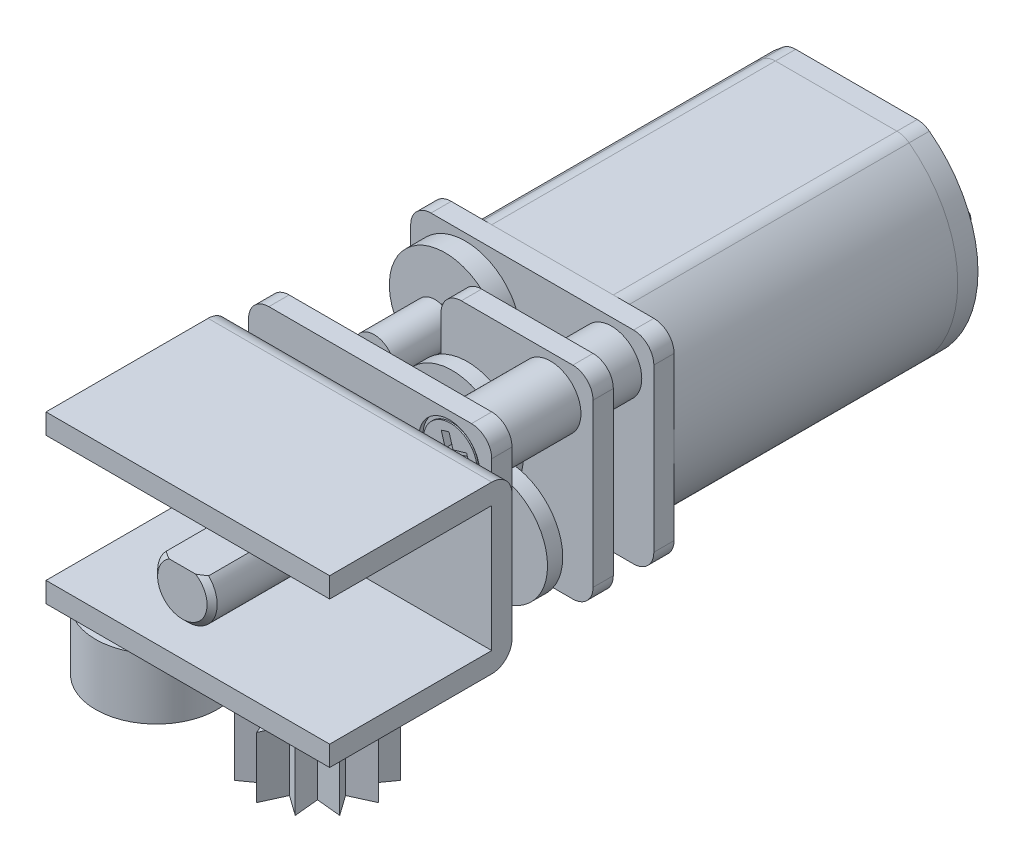
SolidWorks part; units mm, degrees
note: The reader was unsure of these and kept them because the rebuilt part matched: shared geometry of "Sketch2<2>", "Sketch9<3>", "Sketch12<2>", "Sketch29<3>".
material "Plain Carbon Steel"
ref_plane "Front Plane" through (0, 0, 0) normal (0, 0, 1) x (1, 0, 0)
ref_plane "Top Plane" through (0, 0, 0) normal (0, 1, 0) x (1, 0, 0)
ref_plane "Right Plane" through (0, 0, 0) normal (1, 0, 0) x (0, 0, -1)
sketch "Sketch1" plane through (0, 0, 0) normal (0, 0, 1) x (1, 0, 0)
  line L0 (3.3166, 5) -> (-3.3166, 5)
  line L1 (-3.3166, -5) -> (3.3166, -5)
  arc A0 (3.3166, -5) -> (3.3166, 5) centre (0, 0) ccw
  arc A1 (-3.3166, 5) -> (-3.3166, -5) centre (0, 0) ccw
  dimension "D1" = 12
  dimension "D2" = 10
extrude "Boss-Extrude1" add sketch "Sketch1" along normal mid plane 15
fillet "Fillet3" radius 1 4 edges at (-3.3166, -5, 0) (3.3166, -5, 0) (3.3166, 5, 0) (-3.3166, 5, 0)
sketch "Sketch2" plane through (0, 0, 7.5) normal (0, 0, 1) x (1, 0, 0)
  line L1 (-5, -5) -> (5, -5)
  line L2 (-6, -4) -> (-6, 4)
  line L3 (-5, 5) -> (5, 5)
  line L4 (6, -4) -> (6, 4)
  line L5 (-6, -5) -> (6, 5) construction
  line L6 (-6, 5) -> (6, -5) construction
  arc A0 (-5, -5) -> (-6, -4) centre (-5, -4) cw
  arc A1 (5, -5) -> (6, -4) centre (5, -4) ccw
  arc A2 (5, 5) -> (6, 4) centre (5, 4) cw
  arc A3 (-6, 4) -> (-5, 5) centre (-5, 4) cw
  point P0 (0, 0)
  dimension "D3" = 1
  dimension "D1" = 12
  dimension "D2" = 10
extrude "Boss-Extrude2" add sketch "Sketch2" along normal blind 1 separate body
extrude "Boss-Extrude3" add sketch "Sketch2<2>" against normal blind 1 from offset 9 separate body
sketch "Sketch2<2>" plane through (0, 0, 7.5) normal (0, 0, 1) x (1, 0, 0) same geometry as "Sketch2"
sketch "Sketch7" plane through (0, 0, 8.5) normal (0, 0, 1) x (1, 0, 0)
  line L0 (-3.1041, 2.1041) -> (3.1041, -2.1041) construction
  line L1 (0, 0) -> (0, 50000) construction
  line L2 (-6, 4) -> (-6, -4) construction
  line L3 (5, 5) -> (-5, 5) construction
  circle A0 centre (0, 0) radius 3.75 construction
  circle A1 centre (-3.1041, 2.1041) radius 0.5
  circle A2 centre (3.1041, -2.1041) radius 0.5
  circle A3 centre (-3.1041, 2.1041) radius 2.8959 construction
  point P3 (3.1041, -2.1041)
  point P4 (-3.1041, 2.1041)
  dimension "D1" = 7.5
  dimension "D3" = 1
extrude "Boss-Extrude5" add sketch "Sketch7" along normal up to surface (8 mm away) separate body up to face at (0, 0, 16.5)
sketch "Sketch11" plane through (0, 0, 8.5) normal (0, 0, 1) x (1, 0, 0)
  line L0 (-5, -1.25) -> (-2.5, -1.25)
  line L1 (-1.5, -0.25) -> (-1.5, 4)
  line L4 (-5, -5) -> (5, -5)
  line L5 (6, -4) -> (6, 4)
  line L6 (5, 5) -> (-5, 5)
  line L7 (-6, 4) -> (-6, -4)
  line L8 (-5, -5) -> (5, -5)
  line L9 (6, -4) -> (6, 4)
  line L10 (5, 5) -> (-0.5, 5)
  line L11 (-6, -2.25) -> (-6, -4)
  arc A0 (-1.5, 4) -> (-0.5, 5) centre (-0.5, 4) cw
  arc A1 (-2.5, -1.25) -> (-1.5, -0.25) centre (-2.5, -0.25) ccw
  arc A2 (-5, -1.25) -> (-6, -2.25) centre (-5, -2.25) ccw
  arc A4 (-6, -4) -> (-5, -5) centre (-5, -4) ccw
  arc A5 (5, -5) -> (6, -4) centre (5, -4) ccw
  arc A6 (6, 4) -> (5, 5) centre (5, 4) ccw
  arc A7 (-5, 5) -> (-6, 4) centre (-5, 4) ccw
  arc A8 (-6, -4) -> (-5, -5) centre (-5, -4) ccw
  arc A9 (5, -5) -> (6, -4) centre (5, -4) ccw
  arc A10 (6, 4) -> (5, 5) centre (5, 4) ccw
  dimension "D2" = 1
  dimension "D3" = 7.5
  dimension "D4" = 3.75
  dimension "D1" = 0
extrude "Boss-Extrude8" add sketch "Sketch11" along normal blind 1 from offset 2 separate body
sketch "Sketch5" plane through (0, 0, 16.5) normal (0, 0, 1) x (1, 0, 0)
  line L0 (5, 4) -> (-5, -4) construction
  circle A0 centre (0, 0) radius 0.75
  circle A1 centre (-3.1041, 2.1041) radius 0.38
  circle A2 centre (3.1041, -2.1041) radius 0.38
  circle A3 centre (0, 0) radius 5 construction
  circle A4 centre (3.9043, 3.1235) radius 0.75
  circle A5 centre (-3.9043, -3.1235) radius 0.75
  circle A6 centre (0, 0) radius 5.75 construction
  dimension "D1" = 1.5
  dimension "D2" = 0.76
  dimension "D3" = 11.5
  dimension "D4" = 1.5
extrude "Cut-Extrude1" cut sketch "Sketch5" against normal up to surface (9 mm away)
sketch "Sketch8" plane through (0, 0, 16.5) normal (0, 0, 1) x (1, 0, 0)
  circle A0 centre (-3.1041, 2.1041) radius 0.5
  circle A1 centre (3.1041, -2.1041) radius 0.5
  circle A2 centre (-3.1041, 2.1041) radius 0.5 construction
  circle A3 centre (-3.1041, 2.1041) radius 0.38
  circle A4 centre (3.1041, -2.1041) radius 0.38
  circle A5 centre (-3.1041, 2.1041) radius 0.38 construction
extrude "Cut-Extrude2" cut sketch "Sketch8" against normal blind 1
sketch "Sketch9" plane through (0, 0, 8.5) normal (0, 0, 1) x (1, 0, 0)
  circle A0 centre (-3.1041, 2.1041) radius 2.75
  circle A1 centre (-3.1041, 2.1041) radius 0.5
  circle A2 centre (-3.1041, 2.1041) radius 0.5 construction
  circle A3 centre (0, 0) radius 1
  circle M1 centre (0, 0) radius 0.75
  dimension "D1" = 5.5
  dimension "D2" = 2
extrude "Boss-Extrude6" add sketch "Sketch9" along normal blind 1 from offset 0.2 separate body contours A0 A1
extrude "Boss-Extrude16" add sketch "Sketch9<3>" along normal blind 1.3 from offset 0.1 separate body contours A3 M1 | M1
sketch "Sketch9<3>" plane through (0, 0, 8.5) normal (0, 0, 1) x (1, 0, 0) same geometry as "Sketch9"
sketch "Sketch6" plane through (0, 0, 16.5) normal (0, 0, 1) x (1, 0, 0)
  circle A0 centre (0, 0) radius 1.95
  circle A1 centre (0, 0) radius 0.75
  circle A2 centre (0, 0) radius 0.75 construction
  dimension "D1" = 3.9
extrude "Boss-Extrude4" add sketch "Sketch6" along normal blind 0.6
sketch "Sketch10" plane through (0, 0, 9.7) normal (0, 0, 1) x (1, 0, 0)
  circle A0 centre (-3.1041, 2.1041) radius 0.5
  circle A1 centre (-3.1041, 2.1041) radius 1
  circle A2 centre (0, 0) radius 2.75 construction
  circle A4 centre (-3.1041, 2.1041) radius 0.5 construction
  circle A5 centre (-3.1041, 2.1041) radius 2.75 construction
extrude "Boss-Extrude7" add sketch "Sketch10" along normal blind 3 from offset 0.5 separate body
sketch "Sketch12" plane through (0, 0, 8.5) normal (0, 0, 1) x (1, 0, 0)
  circle A0 centre (-3.9043, -3.1235) radius 0.75
  circle A1 centre (-3.9043, -3.1235) radius 1.5
  circle A2 centre (-3.9043, -3.1235) radius 0.75 construction
  circle A3 centre (3.9043, 3.1235) radius 0.75
  circle A4 centre (3.9043, 3.1235) radius 1.5
  dimension "D1" = 3
extrude "Boss-Extrude9" add sketch "Sketch12" along normal up to next (2 mm away) separate body
extrude "Boss-Extrude10" add sketch "Sketch12<2>" along normal up to next (7 mm away) from surface at 3 separate body starting at face at (0.75, 0, 11.5)
sketch "Sketch12<2>" plane through (0, 0, 8.5) normal (0, 0, 1) x (1, 0, 0) same geometry as "Sketch12"
sketch "Sketch13" plane through (0, 0, 17.1) normal (0, 0, 1) x (1, 0, 0)
  circle A0 centre (0, 0) radius 1.5
  dimension "D1" = 3
extrude "Cut-Extrude3" cut sketch "Sketch13" against normal up to next (7.2 mm away)
sketch "Sketch14" plane through (0, 0, 16.5) normal (0, 0, 1) x (1, 0, 0)
  circle A0 centre (3.9043, 3.1235) radius 1.5
  circle A1 centre (-3.9043, -3.1235) radius 1.5
  dimension "D1" = 3
extrude "Cut-Extrude4" cut sketch "Sketch14" against normal blind 0.2
chamfer "Chamfer1" distance 0.5 angle 45 2 edges at (-3.1543, -3.1235, 16.3) (4.6543, 3.1235, 16.3)
sketch "Sketch15" plane through (0, 0, 11.5) normal (0, 0, 1) x (1, 0, 0)
  circle A0 centre (0, 0) radius 2.75
  circle A1 centre (-3.1041, 2.1041) radius 1 construction
extrude "Boss-Extrude11" add sketch "Sketch15" along normal blind 0.75 from offset 0.2 separate body
sketch "Sketch16" plane through (0, 0, 12.45) normal (0, 0, 1) x (1, 0, 0)
  circle A0 centre (0, 0) radius 1
  circle A2 centre (0, 0) radius 1 construction
extrude "Boss-Extrude12" add sketch "Sketch16" along normal blind 1.15 from offset 0.2
sketch "Sketch17" plane through (0, 0, 12.45) normal (0, 0, 1) x (1, 0, 0)
  circle A0 centre (3.1041, -2.1041) radius 2.75
  circle A2 centre (0, 0) radius 1 construction
extrude "Boss-Extrude13" add sketch "Sketch17" along normal blind 0.75 from offset 0.4 separate body
sketch "Sketch18" plane through (0, 0, 13.6) normal (0, 0, 1) x (1, 0, 0)
  circle A0 centre (3.1041, -2.1041) radius 1
  circle A1 centre (0, 0) radius 1 construction
extrude "Boss-Extrude14" add sketch "Sketch18" along normal blind 1.5 from offset 0.2
sketch "Sketch19" plane through (0, 0, 15.3) normal (0, 0, 1) x (1, 0, 0)
  circle A0 centre (3.1041, -2.1041) radius 0.5
  circle A1 centre (3.1041, -2.1041) radius 0.5 construction
extrude "Cut-Extrude5" cut sketch "Sketch19" against normal through all
sketch "Sketch20" plane through (0, 0, 15.3) normal (0, 0, 1) x (1, 0, 0)
  circle A0 centre (0, 0) radius 2.75
  circle A1 centre (3.1041, -2.1041) radius 1 construction
extrude "Boss-Extrude15" add sketch "Sketch20" against normal blind 1 separate body
sketch "Sketch21" plane through (0, 0, 15.3) normal (0, 0, 1) x (1, 0, 0)
  circle A0 centre (0, 0) radius 0.5
  dimension "D1" = 1
extrude "Cut-Extrude6" cut sketch "Sketch21" against normal up to surface (7.8 mm away)
sketch "Sketch22" plane through (0, 0, 0) normal (0, 1, 0) x (1, 0, 0)
  line L0 (0, 0) -> (0, -50000) construction
  line L1 (-3, 7.5) -> (3, 7.5) construction
  line L2 (-0.5, -7.5) -> (-0.5, -15.3)
  line L3 (0.75, -7.5) -> (-0.75, -7.5) construction
  line L4 (-0.5, -15.3) -> (0.5, -15.3) construction
  line L5 (-0.5, -15.3) -> (-1.47, -15.3)
  line L6 (-2.75, -15.3) -> (2.75, -15.3) construction
  line L7 (-1.47, -15.3) -> (-1.47, -25.77)
  line L8 (-1.47, -25.77) -> (0, -25.77)
  line L9 (0, -25.77) -> (0, -7.5)
  line L10 (3, -7.5) -> (-3, -7.5) construction
  line L11 (0, -7.5) -> (-0.5, -7.5)
  line L12 (5, -16.5) -> (-5, -16.5) construction
  point P4 (0, 7.5)
  dimension "D1" = 1
  dimension "D2" = 2.94
  dimension "D3" = 9.27
revolve "Revolve1" add sketch "Sketch22" angle 360 about L0
chamfer "Chamfer2" distance 0.25 angle 45 1 edges at (-1.47, 0, 25.77)
sketch "Sketch23" plane through (0, 0, 25.77) normal (0, 0, 1) x (1, 0, 0)
  line L0 (1.0488, 1.03) -> (-1.0488, 1.03)
  circle A0 centre (0, 0) radius 1.47 construction
  arc A1 (1.0488, 1.03) -> (-1.0488, 1.03) centre (0, 0) ccw
  point P4 (0, -1.47)
  dimension "D1" = 2.5
extrude "Cut-Extrude7" cut sketch "Sketch23" against normal up to surface (8.67 mm away) up to face at (1.5, 0, 17.1)
sketch "Sketch24" plane through (0, 0, 16.5) normal (0, 0, 1) x (1, 0, 0)
  circle A0 centre (4.5, 0) radius 0.8
  circle A1 centre (-4.5, 0) radius 0.8
  dimension "D3" = 1.6
  dimension "D1" = 4.5
  dimension "D2" = 9
extrude "Cut-Extrude8" cut sketch "Sketch24" against normal up to next (1 mm away)
sketch "Sketch25" plane through (0, 0, -7.5) normal (0, 0, -1) x (-1, 0, 0)
  line L2 (-3, -5) -> (3, -5)
  line L3 (3, 5) -> (-3, 5)
  line L4 (-3, -5) -> (3, -5)
  line L5 (3, 5) -> (-3, 5)
  arc A2 (-3.6, 4.8) -> (-3.6, -4.8) centre (0, 0) ccw
  arc A3 (3.6, -4.8) -> (3.6, 4.8) centre (0, 0) ccw
  arc A4 (-3.6, 4.8) -> (-3.6, -4.8) centre (0, 0) ccw
  arc A5 (3.6, -4.8) -> (3.6, 4.8) centre (0, 0) ccw
  arc A10 (3, -5) -> (3.6, -4.8) centre (3, -4) ccw
  arc A11 (3, -5) -> (3.6, -4.8) centre (3, -4) ccw
  arc A12 (3.6, 4.8) -> (3, 5) centre (3, 4) ccw
  arc A13 (3.6, 4.8) -> (3, 5) centre (3, 4) ccw
  arc A14 (-3, 5) -> (-3.6, 4.8) centre (-3, 4) ccw
  arc A15 (-3, 5) -> (-3.6, 4.8) centre (-3, 4) ccw
  arc A16 (-3.6, -4.8) -> (-3, -5) centre (-3, -4) ccw
  arc A17 (-3.6, -4.8) -> (-3, -5) centre (-3, -4) ccw
  dimension "D1" = 0
extrude "Cut-Extrude9" cut sketch "Sketch25" against normal blind 1
sketch "Sketch26" plane through (0, 0, -6.5) normal (0, 0, -1) x (-1, 0, 0)
  line L2 (-3, -5) -> (3, -5)
  line L3 (3, 5) -> (-3, 5)
  line L4 (-3, -5) -> (3, -5)
  line L5 (3, 5) -> (-3, 5)
  arc A2 (-3.6, 4.8) -> (-3.6, -4.8) centre (0, 0) ccw
  arc A3 (3.6, -4.8) -> (3.6, 4.8) centre (0, 0) ccw
  arc A4 (-3.6, 4.8) -> (-3.6, -4.8) centre (0, 0) ccw
  arc A5 (3.6, -4.8) -> (3.6, 4.8) centre (0, 0) ccw
  arc A10 (-3.6, -4.8) -> (-3, -5) centre (-3, -4) ccw
  arc A11 (-3.6, -4.8) -> (-3, -5) centre (-3, -4) ccw
  arc A12 (3, -5) -> (3.6, -4.8) centre (3, -4) ccw
  arc A13 (3, -5) -> (3.6, -4.8) centre (3, -4) ccw
  arc A14 (3.6, 4.8) -> (3, 5) centre (3, 4) ccw
  arc A15 (3.6, 4.8) -> (3, 5) centre (3, 4) ccw
  arc A16 (-3, 5) -> (-3.6, 4.8) centre (-3, 4) ccw
  arc A17 (-3, 5) -> (-3.6, 4.8) centre (-3, 4) ccw
  dimension "D1" = 0
extrude "Boss-Extrude17" add sketch "Sketch26" along normal blind 1 separate body
sketch "Sketch27" plane through (0, 0, -7.5) normal (0, 0, -1) x (-1, 0, 0)
  circle A0 centre (0, 0) radius 2.5
  dimension "D1" = 5
extrude "Boss-Extrude18" add sketch "Sketch27" along normal blind 1.5
sketch "Sketch28" plane through (0, 0, -7.5) normal (0, 0, -1) x (-1, 0, 0)
  line L1 (3.35, 0.75) -> (3.65, 0.75)
  line L2 (3.35, 0.75) -> (3.35, -0.75)
  line L3 (3.35, -0.75) -> (3.65, -0.75)
  line L4 (3.65, 0.75) -> (3.65, -0.75)
  line L5 (3.35, 0.75) -> (3.65, -0.75) construction
  line L6 (3.35, -0.75) -> (3.65, 0.75) construction
  line L7 (-3.65, 0.75) -> (-3.35, 0.75)
  line L8 (-3.65, 0.75) -> (-3.65, -0.75)
  line L9 (-3.65, -0.75) -> (-3.35, -0.75)
  line L10 (-3.35, 0.75) -> (-3.35, -0.75)
  line L11 (-3.65, 0.75) -> (-3.35, -0.75) construction
  line L12 (-3.65, -0.75) -> (-3.35, 0.75) construction
  point P0 (3.5, 0)
  point P5 (-3.5, 0)
  dimension "D1" = 3.5
  dimension "D2" = 7
  dimension "D3" = 0.3
  dimension "D4" = 1.5
extrude "Boss-Extrude19" add sketch "Sketch28" along normal blind 2 separate body
fillet "Fillet1" radius 0.7 2 edges at (-3.5, -0.75, -9.5) (-3.5, 0.75, -9.5)
fillet "Fillet2" radius 0.7 2 edges at (3.5, -0.75, -9.5) (3.5, 0.75, -9.5)
ref_plane "Plane1" through (0, 0, 0) normal (0.6247, -0.7809, 0) x (0.7809, 0.6247, 0)
sketch "Sketch29" plane through (0, 0, 0) normal (0.6247, -0.7809, 0) x (0.7809, 0.6247, 0)
  line L0 (5, 16.5) -> (5, 50016.5) construction
  line L1 (6.5, 16.5) -> (3.5, 16.5) construction
  line L2 (-5, 16.5) -> (-5, 50016.5) construction
  line L3 (-3.5, 16.5) -> (-6.5, 16.5) construction
  line L4 (5.7, 7.5) -> (5.7, 15.755)
  line L5 (6, 7.5) -> (-0.1874, 7.5) construction
  line L6 (5.7, 15.755) -> (6.325, 16.38)
  line L7 (6.325, 16.38) -> (6.325, 16.45)
  line L8 (6.325, 16.45) -> (5, 16.45)
  line L9 (5, 16.45) -> (5, 7.5)
  line L10 (4.25, 7.5) -> (5.75, 7.5) construction
  line L11 (5, 7.5) -> (5.7, 7.5)
  line L12 (2.1864, 16.5) -> (7.184, 16.5) construction
  line L13 (0, 0) -> (0, 50000) construction
  line L14 (-5, 7.5) -> (-5.7, 7.5)
  line L15 (-5, 16.45) -> (-5, 7.5)
  line L16 (-6.325, 16.45) -> (-5, 16.45)
  line L17 (-6.325, 16.38) -> (-6.325, 16.45)
  line L18 (-5.7, 15.755) -> (-6.325, 16.38)
  line L19 (-5.7, 7.5) -> (-5.7, 15.755)
  point P4 (5, 16.5)
  point P9 (-5, 16.5)
  dimension "D1" = 45
  dimension "D2" = 1.4
  dimension "D3" = 2.65
  dimension "D4" = 0.05
  dimension "D5" = 0.07
revolve "Revolve2" add sketch "Sketch29" angle 360 about L0
revolve "Revolve3" add sketch "Sketch29<3>" angle 360 about L2
sketch "Sketch29<3>" plane through (0, 0, 0) normal (0.6247, -0.7809, 0) x (0.7809, 0.6247, 0) same geometry as "Sketch29"
sketch "Sketch30" plane through (0, 0, 16.45) normal (0, 0, 1) x (1, 0, 0)
  line L0 (-3.5871, -2.2813) -> (-4.2216, -3.9657) construction
  line L1 (-3.7742, -2.2107) -> (-4.021, -2.8658)
  line L2 (-4.7466, -2.8062) -> (-3.0621, -3.4408) construction
  line L3 (-4.8171, -2.9934) -> (-4.162, -3.2401)
  line L4 (-3.3999, -2.3518) -> (-3.6467, -3.0068)
  line L5 (-4.6761, -2.619) -> (-4.021, -2.8658)
  line L6 (-3.7742, -2.2107) -> (-3.3999, -2.3518)
  line L7 (-4.4088, -3.8952) -> (-4.0345, -4.0362)
  line L8 (-4.8171, -2.9934) -> (-4.6761, -2.619)
  line L9 (-3.1326, -3.6279) -> (-2.9916, -3.2536)
  line L10 (-4.162, -3.2401) -> (-4.4088, -3.8952)
  line L11 (-3.7742, -2.2107) -> (-4.4088, -3.8952) construction
  line L12 (-3.6467, -3.0068) -> (-2.9916, -3.2536)
  line L13 (-4.6761, -2.619) -> (-2.9916, -3.2536) construction
  line L14 (-3.7877, -3.3811) -> (-4.0345, -4.0362)
  line L15 (-3.3999, -2.3518) -> (-4.0345, -4.0362) construction
  line L16 (-3.7877, -3.3811) -> (-3.1326, -3.6279)
  line L17 (-4.8171, -2.9934) -> (-3.1326, -3.6279) construction
  line L18 (3.6482, 3.9863) -> (4.1605, 2.2607) construction
  line L19 (3.0416, 2.8674) -> (4.7671, 3.3796) construction
  line L20 (3.4565, 3.9293) -> (3.6557, 3.2583)
  line L21 (3.0985, 2.6756) -> (3.7695, 2.8748)
  line L22 (3.84, 4.0432) -> (4.0392, 3.3721)
  line L23 (2.9846, 3.0591) -> (3.6557, 3.2583)
  line L24 (3.4565, 3.9293) -> (3.84, 4.0432)
  line L25 (3.9687, 2.2038) -> (4.3522, 2.3176)
  line L26 (3.0985, 2.6756) -> (2.9846, 3.0591)
  line L27 (4.824, 3.1879) -> (4.7102, 3.5713)
  line L28 (4.0392, 3.3721) -> (4.7102, 3.5713)
  line L29 (2.9846, 3.0591) -> (4.7102, 3.5713) construction
  line L30 (3.7695, 2.8748) -> (3.9687, 2.2038)
  line L31 (3.4565, 3.9293) -> (3.9687, 2.2038) construction
  line L32 (4.153, 2.9887) -> (4.824, 3.1879)
  line L33 (3.0985, 2.6756) -> (4.824, 3.1879) construction
  line L34 (4.153, 2.9887) -> (4.3522, 2.3176)
  line L35 (3.84, 4.0432) -> (4.3522, 2.3176) construction
  point P2 (-3.9043, -3.1235)
  point P15 (3.9043, 3.1235)
  dimension "D1" = 1.8
  dimension "D2" = 0.2
  dimension "D3" = 0.2
  dimension "D4" = 0.2
  dimension "D5" = 0.2
extrude "Cut-Extrude10" cut sketch "Sketch30" against normal blind 0.4
sketch "Sketch31" plane through (0, 0, 0) normal (1, 0, 0) x (0, 0, -1)
  line L0 (-16.5, 3) -> (-16.5, -3.2)
  line L1 (-17.5, -4.2) -> (-25.5, -4.2)
  line L2 (-17.5, 4) -> (-25.5, 4)
  arc A0 (-16.5, -3.2) -> (-17.5, -4.2) centre (-17.5, -3.2) cw
  arc A1 (-16.5, 3) -> (-17.5, 4) centre (-17.5, 3) ccw
  point P8 (-16.5, -4.2)
  point P11 (-16.5, 4)
extrude "Extrude-Thin1" add sketch "Sketch31" along normal blind 7 and the other way blind 7 thin
sketch "Sketch32" plane through (0, -4.2, 0) normal (0, -1, 0) x (1, 0, 0)
  line L0 (3.2, 25.3) -> (2.6941, 24.1882)
  line L4 (4.7, 24.8981) -> (3.7059, 24.1882)
  line L5 (3.2, 25.3) -> (3.7059, 24.1882)
  line L6 (4.7, 24.8981) -> (4.5822, 23.6822)
  line L7 (5.7981, 23.8) -> (4.5822, 23.6822)
  line L8 (5.7981, 23.8) -> (5.0882, 22.8059)
  line L9 (6.2, 22.3) -> (5.0882, 22.8059)
  line L10 (6.2, 22.3) -> (5.0882, 21.7941)
  line L11 (5.7981, 20.8) -> (5.0882, 21.7941)
  line L12 (5.7981, 20.8) -> (4.5822, 20.9178)
  line L13 (4.7, 19.7019) -> (4.5822, 20.9178)
  line L14 (4.7, 19.7019) -> (3.7059, 20.4118)
  line L15 (3.2, 19.3) -> (3.7059, 20.4118)
  line L16 (3.2, 19.3) -> (2.6941, 20.4118)
  line L17 (1.7, 19.7019) -> (2.6941, 20.4118)
  line L18 (1.7, 19.7019) -> (1.8178, 20.9178)
  line L19 (0.6019, 20.8) -> (1.8178, 20.9178)
  line L20 (0.6019, 20.8) -> (1.3118, 21.7941)
  line L21 (0.2, 22.3) -> (1.3118, 21.7941)
  line L22 (0.2, 22.3) -> (1.3118, 22.8059)
  line L23 (0.6019, 23.8) -> (1.3118, 22.8059)
  line L24 (0.6019, 23.8) -> (1.8178, 23.6822)
  line L25 (1.7, 24.8981) -> (1.8178, 23.6822)
  line L26 (1.7, 24.8981) -> (2.6941, 24.1882)
  circle A1 centre (-4.75, 22.3) radius 3
  point P42 (3.2, 22.3)
extrude "Boss-Extrude20" add sketch "Sketch32" along normal blind 3 from offset 0.5 separate body
